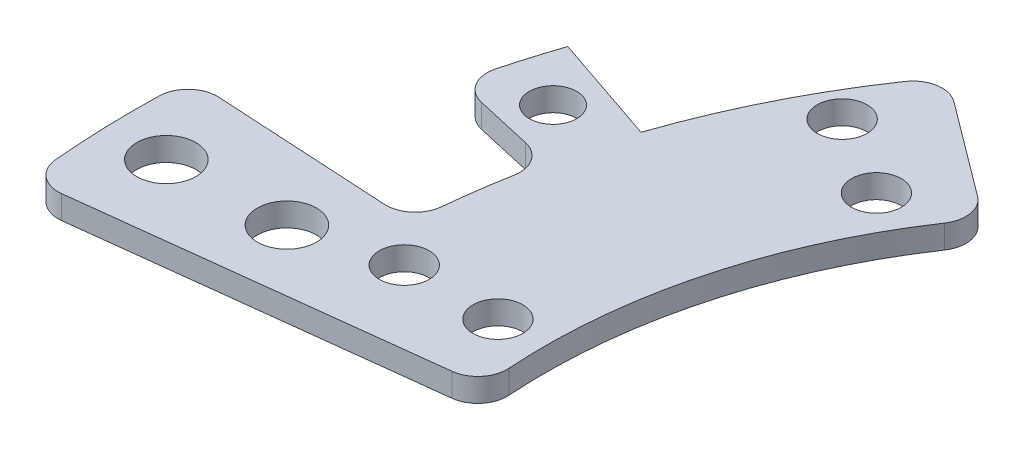
SolidWorks part; units mm, degrees
ref_plane "Front Plane" through (0, 0, 0) normal (0, 0, 1) x (1, 0, 0)
ref_plane "Top Plane" through (0, 0, 0) normal (0, 1, 0) x (1, 0, 0)
ref_plane "Right Plane" through (0, 0, 0) normal (1, 0, 0) x (0, 0, -1)
sketch "Sketch1" plane through (0, 0, 0) normal (0, 1, 0) x (1, 0, 0)
  line L0 (0, 0) -> (-59, 0) construction
  line L1 (0, 0) -> (-51.0955, 29.5) construction
  line L2 (-37.6558, 28.1254) -> (-49.6736, 37.1016)
  line L3 (-46.6736, -5.5294) -> (-61.5694, -7.2941)
  circle A0 centre (0, 0) radius 51 construction
  circle A1 centre (0, 0) radius 59 construction
  circle A2 centre (-44.1673, 25.5) radius 2.125
  circle A3 centre (-51.0955, 29.5) radius 2.125
  circle A4 centre (-59, 0) radius 2.125
  circle A5 centre (-51, 0) radius 2.125
  arc A6 (-37.6558, 28.1254) -> (-46.6736, -5.5294) centre (0, 0) ccw
  arc A7 (-49.6736, 37.1016) -> (-61.5694, -7.2941) centre (0, 0) ccw
  point P5 (-44.1673, 25.5)
  point P7 (-51, 0)
  dimension "D1" = 102
  dimension "D2" = 118
  dimension "D4" = 4.25
  dimension "D5" = 47
  dimension "D8" = 6
  dimension "D3" = 30
  dimension "D6" = 15
  dimension "D7" = 6
extrude "Boss-Extrude1" add sketch "Sketch1" along normal blind 2
sketch "Sketch3" plane through (0, 0, 0) normal (0, 1, 0) x (1, 0, 0)
  line L1 (-70.2229, 15.898) -> (-60.4697, 13.6899)
  line L2 (0, 0) -> (-68.1764, 23.1512) construction
  line L3 (-68.1764, 23.1512) -> (-58.7075, 19.9357)
  line L4 (-37.6558, 28.1254) -> (-49.6736, 37.1016) construction
  arc A2 (-49.6736, 37.1016) -> (-61.5694, -7.2941) centre (0, 0) ccw construction
  arc A3 (-70.2229, 15.898) -> (-68.1764, 23.1512) centre (0, 0) cw
  arc A4 (-60.4697, 13.6899) -> (-58.7075, 19.9357) centre (0, 0) cw
  dimension "D1" = 6
  dimension "D2" = 10
  dimension "D3" = 18
extrude "Boss-Extrude3" add sketch "Sketch3" along normal up to surface (2 mm away) up to face at (-44.1673, 2, -23.375)
sketch "Sketch4" plane through (0, 2, 0) normal (0, 1, 0) x (1, 0, 0)
  line L0 (-69.2946, 19.5514) -> (0, 0) construction
  arc A0 (-68.1764, 23.1512) -> (-70.2229, 15.898) centre (0, 0) ccw construction
  circle A2 centre (-64.4825, 18.1936) radius 2.025
  dimension "D1" = 4.05
  dimension "D2" = 67
extrude "Cut-Extrude1" cut sketch "Sketch4" against normal through all both and the other way through all
sketch "Sketch6" plane through (0, 0, 0) normal (0, 1, 0) x (1, 0, 0)
  line L0 (-61.5694, -7.2941) -> (-81.4305, -9.6471)
  line L1 (-81.8686, 4.6398) -> (-61.9007, 3.5081)
  line L2 (-81.9615, -2.5132) -> (0, 0) construction
  arc A0 (-81.4305, -9.6471) -> (-81.8686, 4.6398) centre (0, 0) cw
  arc A1 (-60.4697, 13.6899) -> (-61.5694, -7.2941) centre (0, 0) ccw construction
  arc A2 (-61.9007, 3.5081) -> (-61.5694, -7.2941) centre (0, 0) ccw
  circle A3 centre (-76.9638, -2.36) radius 2.525
  circle A4 centre (-66.9685, -2.0535) radius 2.525
  dimension "D3" = 5.05
  dimension "D4" = 10
  dimension "D5" = 67
  dimension "D1" = 20
  dimension "D2" = 10
extrude "Boss-Extrude4" add sketch "Sketch6" along normal up to surface (2 mm away) up to face at (-64.4825, 2, -16.1686)
fillet "Fillet1" radius 2.5 8 edges at (-46.6736, 1, 5.5294) (-70.2229, 1, -15.898) (-60.4697, 1, -13.6899) (-37.6558, 1, -28.1254) (-49.6736, 1, -37.1016) (-61.9007, 1, -3.5081) (-81.4305, 1, 9.6471) (-81.8686, 1, -4.6398)
